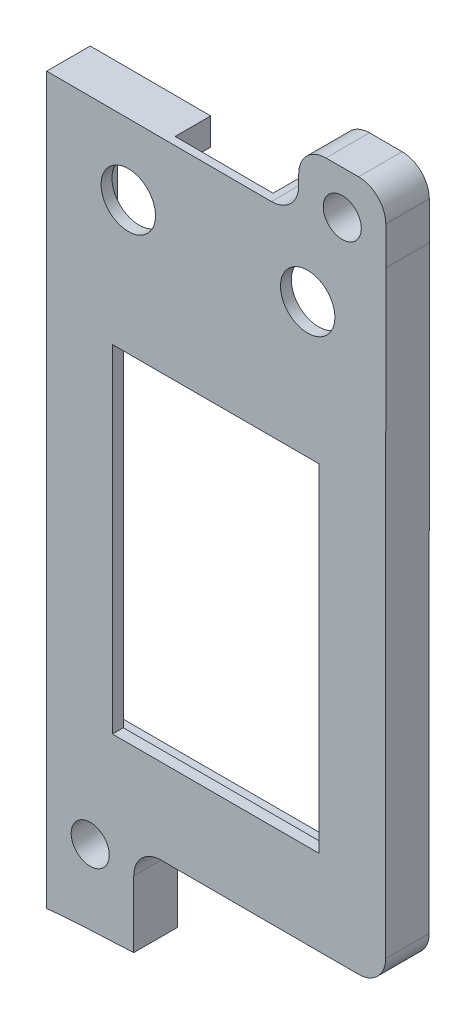
SolidWorks part; units mm, degrees
ref_plane "Front" through (0, 0, 0) normal (0, 0, 1) x (1, 0, 0)
ref_plane "Top" through (0, 0, 0) normal (0, 1, 0) x (1, 0, 0)
ref_plane "Side" through (0, 0, 0) normal (1, 0, 0) x (0, 0, -1)
ref_axis "X_Axis" through (-20.1896, 0, 0) along (1, 0, 0)
ref_axis "Y_Axis" through (0, -14.8261, 0) along (0, 1, 0)
ref_axis "Z_Axis" through (0, 0, -19.842) along (0, 0, 1)
sketch "Sketch1" plane through (0, 0, 0) normal (0, 0, 1) x (1, 0, 0)
  line L0 (-12.1762, 17.3557) -> (13.9737, 17.3297) construction
  line L1 (13.9737, 17.3297) -> (13.9859, 69.814) construction
  line L2 (13.9859, 69.814) -> (-12.1762, 69.8802) construction
  line L3 (-12.1762, 69.8802) -> (-12.1762, 17.3557) construction
  line L4 (-12.1762, 17.3557) -> (13.9737, 17.3297)
  line L5 (13.9737, 17.3297) -> (13.9859, 69.814)
  line L6 (13.9859, 69.814) -> (-12.1762, 69.8802)
  line L7 (-12.1762, 69.8802) -> (-12.1762, 17.3557)
  line L8 (-4.1737, 14.8478) -> (13.9712, 14.8297)
  line L9 (16.4737, 17.3291) -> (16.4865, 72.3076)
  line L10 (16.4865, 72.3076) -> (16.4865, 75.8076)
  line L11 (13.9865, 78.3076) -> (10.9865, 78.3076)
  line L12 (8.4865, 75.8076) -> (8.4865, 74.8342)
  line L13 (5.9802, 72.3342) -> (-14.6762, 72.3865)
  line L14 (-14.6762, 72.3865) -> (-14.6762, 5.7379)
  line L15 (-6.6762, 6.226) -> (-6.6762, 12.3478)
  line L16 (-4.1737, 14.8478) -> (13.9712, 14.8297)
  line L17 (16.4737, 17.3291) -> (16.4865, 72.3076)
  line L18 (16.4865, 72.3076) -> (16.4865, 75.8076)
  line L19 (13.9865, 78.3076) -> (10.9865, 78.3076)
  line L20 (8.4865, 75.8076) -> (8.4865, 74.8342)
  line L21 (5.9802, 72.3342) -> (-14.6762, 72.3865)
  line L22 (-14.6762, 72.3865) -> (-14.6762, 5.7379)
  line L23 (-6.6762, 6.226) -> (-6.6762, 12.3478)
  circle A1 centre (12.487, 74.3178) radius 1.75
  circle A3 centre (-10.6762, 12.8542) radius 1.75
  arc A5 (13.9712, 14.8297) -> (16.4737, 17.3291) centre (13.9737, 17.3297) ccw
  arc A6 (16.4865, 75.8076) -> (13.9865, 78.3076) centre (13.9865, 75.8076) ccw
  arc A7 (10.9865, 78.3076) -> (8.4865, 75.8076) centre (10.9865, 75.8076) ccw
  arc A8 (5.9802, 72.3342) -> (8.4865, 74.8342) centre (5.9865, 74.8342) ccw
  arc A9 (-4.1737, 14.8478) -> (-6.6762, 12.3478) centre (-4.1762, 12.3478) ccw
  arc A10 (13.9712, 14.8297) -> (16.4737, 17.3291) centre (13.9737, 17.3297) ccw
  arc A11 (16.4865, 75.8076) -> (13.9865, 78.3076) centre (13.9865, 75.8076) ccw
  arc A12 (10.9865, 78.3076) -> (8.4865, 75.8076) centre (10.9865, 75.8076) ccw
  arc A13 (5.9802, 72.3342) -> (8.4865, 74.8342) centre (5.9865, 74.8342) ccw
  arc A14 (-4.1737, 14.8478) -> (-6.6762, 12.3478) centre (-4.1762, 12.3478) ccw
  circle A19 centre (12.487, 74.3178) radius 2 construction
  circle A20 centre (-10.6762, 12.8542) radius 2 construction
  spline S1 degree 3 poles (-1041.9803, 3710.0985) (-351.0755, -3224.8791) (-279.4809, -9.8377) (-12.0128, 5.9551) (-11.346, 5.9937) (90.5151, 11.6476) (193.8057, -17.093) (535.2009, -3948.1861) knots -99.788507 -99.788507 -99.788507 -99.788507 0.25 0.25 0.5 0.5 38.435126 38.435126 38.435126 38.435126 only from (-14.6762, 5.7379) to (-6.6762, 6.226)
  spline S2 degree 3 poles (-14.6762, 5.7379) (-14.0119, 5.817) (-13.3463, 5.8764) (-12.0128, 5.9551) (-11.346, 5.9937) (-9.3454, 6.1047) (-8.0112, 6.1728) (-6.6762, 6.226) knots 0 0 0 0 0.25 0.25 0.5 0.5 1 1 1 1
  dimension "D2" = 3.5
  dimension "D3" = 3.5
  dimension "D1" = 0
extrude "Boss-Extrude1" add sketch "Sketch1" along normal blind 1
sketch "Sketch2" plane through (0, 0, 1) normal (0, 0, 1) x (1, 0, 0)
  line L0 (13.9737, 17.3297) -> (13.9859, 69.814) construction
  line L3 (-12.1762, 21.3302) -> (13.9746, 21.3302)
  line L5 (13.9859, 69.814) -> (-12.1762, 69.8802) construction
  line L6 (-12.1762, 69.8802) -> (-12.1762, 17.3557) construction
  line L7 (13.9746, 21.3302) -> (13.9859, 69.814)
  line L8 (13.9859, 69.814) -> (-12.1762, 69.8802)
  line L9 (-12.1762, 69.8802) -> (-12.1762, 21.3302)
  line L13 (-4.1737, 14.8478) -> (13.9712, 14.8297)
  line L14 (16.4737, 17.3291) -> (16.4865, 72.3076)
  line L15 (16.4865, 72.3076) -> (16.4865, 75.8076)
  line L16 (13.9865, 78.3076) -> (10.9865, 78.3076)
  line L17 (8.4865, 75.8076) -> (8.4865, 74.8342)
  line L18 (5.9802, 72.3342) -> (-14.6762, 72.3865)
  line L19 (-14.6762, 72.3865) -> (-14.6762, 5.7379)
  line L20 (-6.6762, 6.226) -> (-6.6762, 12.3478)
  line L21 (-4.1737, 14.8478) -> (13.9712, 14.8297)
  line L22 (16.4737, 17.3291) -> (16.4865, 72.3076)
  line L23 (16.4865, 72.3076) -> (16.4865, 75.8076)
  line L24 (13.9865, 78.3076) -> (10.9865, 78.3076)
  line L25 (8.4865, 75.8076) -> (8.4865, 74.8342)
  line L26 (5.9802, 72.3342) -> (-14.6762, 72.3865)
  line L27 (-14.6762, 72.3865) -> (-14.6762, 5.7379)
  line L28 (-6.6762, 6.226) -> (-6.6762, 12.3478)
  circle A0 centre (12.487, 74.3178) radius 1.75 construction
  circle A1 centre (12.487, 74.3178) radius 1.75
  circle A2 centre (-10.6762, 12.8542) radius 1.75 construction
  circle A3 centre (-10.6762, 12.8542) radius 1.75
  arc A5 (-4.1737, 14.8478) -> (-6.6762, 12.3478) centre (-4.1762, 12.3478) ccw
  arc A6 (13.9712, 14.8297) -> (16.4737, 17.3291) centre (13.9737, 17.3297) ccw
  arc A7 (16.4865, 75.8076) -> (13.9865, 78.3076) centre (13.9865, 75.8076) ccw
  arc A8 (10.9865, 78.3076) -> (8.4865, 75.8076) centre (10.9865, 75.8076) ccw
  arc A9 (5.9802, 72.3342) -> (8.4865, 74.8342) centre (5.9865, 74.8342) ccw
  arc A10 (-4.1737, 14.8478) -> (-6.6762, 12.3478) centre (-4.1762, 12.3478) ccw
  arc A11 (13.9712, 14.8297) -> (16.4737, 17.3291) centre (13.9737, 17.3297) ccw
  arc A12 (16.4865, 75.8076) -> (13.9865, 78.3076) centre (13.9865, 75.8076) ccw
  arc A13 (10.9865, 78.3076) -> (8.4865, 75.8076) centre (10.9865, 75.8076) ccw
  arc A14 (5.9802, 72.3342) -> (8.4865, 74.8342) centre (5.9865, 74.8342) ccw
  spline S1 degree 3 poles (-829.4861, 1721.6177) (-332.3105, -2536.3311) (-249.2014, -8.0498) (-12.0128, 5.9551) (-11.346, 5.9937) (69.3315, 10.4717) (150.6526, -6.5657) (349.9391, -1956.965) knots -88.435055 -88.435055 -88.435055 -88.435055 0.25 0.25 0.5 0.5 30.493929 30.493929 30.493929 30.493929 only from (-14.6762, 5.7379) to (-6.6762, 6.226)
  spline S2 degree 3 poles (-14.6762, 5.7379) (-14.0119, 5.817) (-13.3463, 5.8764) (-12.0128, 5.9551) (-11.346, 5.9937) (-9.3454, 6.1047) (-8.0112, 6.1728) (-6.6762, 6.226) knots 0 0 0 0 0.25 0.25 0.5 0.5 1 1 1 1
  dimension "D1" = 0
extrude "Boss-Extrude2" add sketch "Sketch2" along normal blind 2
sketch "Sketch3" plane through (0, 0, 3) normal (0, 0, 1) x (1, 0, 0)
  line L6 (0.862, 70.6723) -> (0.862, 14.8428) construction
  line L7 (4.032, 70.6723) -> (-2.308, 70.6723) construction
  line L8 (-4.1737, 14.8478) -> (13.9712, 14.8297)
  line L9 (16.4737, 17.3291) -> (16.4865, 72.3076)
  line L10 (16.4865, 72.3076) -> (16.4865, 75.8076)
  line L11 (13.9865, 78.3076) -> (10.9865, 78.3076)
  line L12 (8.4865, 75.8076) -> (8.4865, 74.8342)
  line L13 (5.9802, 72.3342) -> (-14.6762, 72.3865)
  line L14 (-14.6762, 72.3865) -> (-14.6762, 5.7379)
  line L15 (-6.6762, 6.226) -> (-6.6762, 12.3478)
  line L16 (-4.1737, 14.8478) -> (13.9712, 14.8297)
  line L17 (16.4737, 17.3291) -> (16.4865, 72.3076)
  line L18 (16.4865, 72.3076) -> (16.4865, 75.8076)
  line L19 (13.9865, 78.3076) -> (10.9865, 78.3076)
  line L20 (8.4865, 75.8076) -> (8.4865, 74.8342)
  line L21 (5.9802, 72.3342) -> (-14.6762, 72.3865)
  line L22 (-14.6762, 72.3865) -> (-14.6762, 5.7379)
  line L23 (-6.6762, 6.226) -> (-6.6762, 12.3478)
  line L25 (-8.5614, 67.8674) -> (-5.7928, 63.8796) construction
  line L26 (-5.7928, 67.8674) -> (-8.5614, 63.8796) construction
  line L27 (7.9232, 68.0198) -> (10.6918, 64.032) construction
  line L28 (10.362, 53.6482) -> (-8.638, 53.6482)
  line L29 (10.362, 53.6482) -> (10.362, 22.6482)
  line L30 (10.362, 22.6482) -> (-8.638, 22.6482)
  line L31 (-8.638, 53.6482) -> (-8.638, 22.6482)
  line L36 (10.6918, 68.0198) -> (10.6918, 64.032) construction
  line L37 (10.6918, 64.032) -> (10.6918, 68.0198) construction
  line L38 (10.6918, 68.0198) -> (7.9232, 64.032) construction
  line L39 (10.362, 53.6482) -> (-8.638, 22.6482) construction
  line L40 (10.362, 22.6482) -> (-8.638, 53.6482) construction
  circle A0 centre (-7.1771, 65.8735) radius 2.5
  circle A1 centre (9.3075, 66.0259) radius 2.5
  circle A2 centre (12.487, 74.3178) radius 1.75 construction
  circle A3 centre (12.487, 74.3178) radius 1.75
  circle A4 centre (-10.6762, 12.8542) radius 1.75 construction
  arc A5 (-4.1737, 14.8478) -> (-6.6762, 12.3478) centre (-4.1762, 12.3478) ccw
  arc A6 (13.9712, 14.8297) -> (16.4737, 17.3291) centre (13.9737, 17.3297) ccw
  arc A7 (16.4865, 75.8076) -> (13.9865, 78.3076) centre (13.9865, 75.8076) ccw
  arc A8 (10.9865, 78.3076) -> (8.4865, 75.8076) centre (10.9865, 75.8076) ccw
  arc A9 (5.9802, 72.3342) -> (8.4865, 74.8342) centre (5.9865, 74.8342) ccw
  arc A10 (-4.1737, 14.8478) -> (-6.6762, 12.3478) centre (-4.1762, 12.3478) ccw
  arc A11 (13.9712, 14.8297) -> (16.4737, 17.3291) centre (13.9737, 17.3297) ccw
  arc A12 (16.4865, 75.8076) -> (13.9865, 78.3076) centre (13.9865, 75.8076) ccw
  arc A13 (10.9865, 78.3076) -> (8.4865, 75.8076) centre (10.9865, 75.8076) ccw
  arc A14 (5.9802, 72.3342) -> (8.4865, 74.8342) centre (5.9865, 74.8342) ccw
  circle A15 centre (-10.6762, 12.8542) radius 1.75
  spline S1 degree 3 poles (-829.4861, 1721.6177) (-332.3105, -2536.3311) (-249.2014, -8.0498) (-12.0128, 5.9551) (-11.346, 5.9937) (69.3315, 10.4717) (150.6526, -6.5657) (349.9391, -1956.965) knots -88.435055 -88.435055 -88.435055 -88.435055 0.25 0.25 0.5 0.5 30.493929 30.493929 30.493929 30.493929 only from (-14.6762, 5.7379) to (-6.6762, 6.226)
  spline S2 degree 3 poles (-14.6762, 5.7379) (-14.0119, 5.817) (-13.3463, 5.8764) (-12.0128, 5.9551) (-11.346, 5.9937) (-9.3454, 6.1047) (-8.0112, 6.1728) (-6.6762, 6.226) knots 0 0 0 0 0.25 0.25 0.5 0.5 1 1 1 1
  point P29 (0.862, 38.1482)
  dimension "D3" = 5
  dimension "D2" = 31
  dimension "D4" = 19
  dimension "D5" = 4
  dimension "D1" = 0
extrude "Boss-Extrude3" add sketch "Sketch3" along normal blind 1
sketch "Sketch5" plane through (-14.6762, 0, 0) normal (-1, 0, 0) x (0, 0, 1)
  line L0 (-1.0102, 47.7252) -> (-1.0102, 67.4902) construction
  line L1 (-1.0102, 55.1394) -> (2.5898, 55.1394)
  line L2 (-1.0102, 55.1394) -> (-1.0102, 59.7394)
  line L3 (-1.0102, 59.7394) -> (2.5898, 59.7394)
  line L4 (2.5898, 55.1394) -> (2.5898, 59.7394)
  line L5 (2.0418, 57.428) -> (-1.0102, 57.4394) construction
  line L6 (2.0418, 55.142) -> (2.0418, 59.714) construction
  dimension "D1" = 3.6
  dimension "D2" = 4.6
extrude "Cut-Extrude1" cut sketch "Sketch5" against normal blind 21
sketch "Sketch6" plane through (0.1831, 72.3489, 0) normal (0.0025, 1, 0) x (1, -0.0025, 0)
  line L1 (-3.7868, -3.2648) -> (5.2084, -3.2648)
  line L2 (-3.7868, -3.2648) -> (-3.7868, 0)
  line L3 (-3.7868, 0) -> (5.2084, 0)
  line L4 (5.2084, -3.2648) -> (5.2084, 0)
extrude "Cut-Extrude2" cut sketch "Sketch6" against normal blind 21
